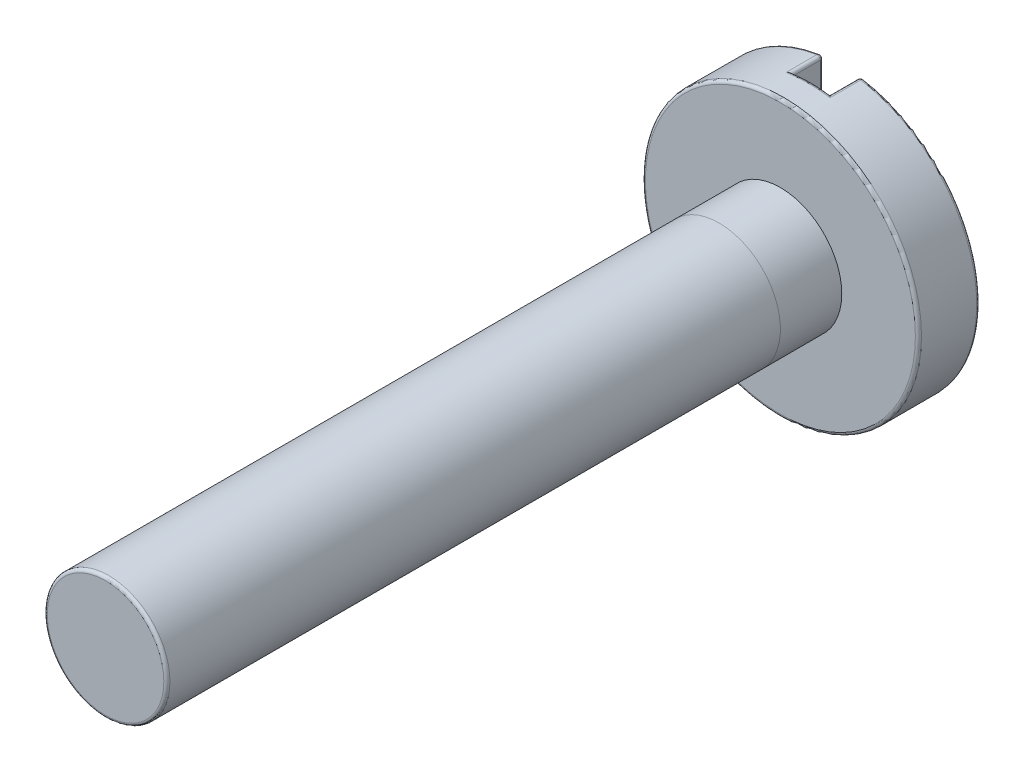
SolidWorks part; units mm, degrees
ref_plane "Front Plane" through (0, 0, 0) normal (0, 0, 1) x (1, 0, 0)
ref_plane "Top Plane" through (0, 0, 0) normal (0, 1, 0) x (1, 0, 0)
ref_plane "Right Plane" through (0, 0, 0) normal (1, 0, 0) x (0, 0, -1)
sketch "Sketch1" plane through (0, 0, 0) normal (0, 0, 1) x (1, 0, 0)
  circle A0 centre (0, 0) radius 1
  dimension "D1" = 2
extrude "Boss-Extrude1" add sketch "Sketch1" along normal blind 11 contours A0
sketch "Sketch2" plane through (0, 0, 0) normal (0, 0, 1) x (1, 0, 0)
  circle A2 centre (0, 0) radius 2.25
  circle A3 centre (0, 0) radius 2.25
  dimension "D1" = 1.25
extrude "Boss-Extrude2" add sketch "Sketch2" against normal blind 1
sketch "Sketch3" plane through (0, 0, -1) normal (0, 0, -1) x (-1, 0, 0)
  line L1 (-0.3, 4.1838) -> (0.3, 4.1838)
  line L2 (-0.3, 4.1838) -> (-0.3, -4.1838)
  line L3 (-0.3, -4.1838) -> (0.3, -4.1838)
  line L4 (0.3, 4.1838) -> (0.3, -4.1838)
  line L5 (-0.3, 4.1838) -> (0.3, -4.1838) construction
  line L6 (-0.3, -4.1838) -> (0.3, 4.1838) construction
  point P0 (0, 0)
  dimension "D1" = 0.6
extrude "Cut-Extrude1" cut sketch "Sketch3" against normal blind 0.5
fillet "Fillet1" radius 0.05 12 edges at (1, 0, 11) (2.25, 0, 0) (-0.3, -2.2299, -0.75) (0, -2.25, -0.5) (0.3, -2.2299, -0.75) (-0.3, 2.2299, -0.75) (0, 2.25, -0.5) (0.3, 2.2299, -0.75) (0.3, 0, -1) (2.25, 0, -1) (-2.25, 0, -1) (-0.3, 0, -1)
sketch "Sketch4" plane through (0, 0, 0) normal (0, 1, 0) x (1, 0, 0)
  line L0 (-4.2772, -1) -> (4.7645, -1)
  line L1 (-0.95, -11) -> (0.95, -11) construction
  dimension "D1" = 10
split line "Split Line1"
